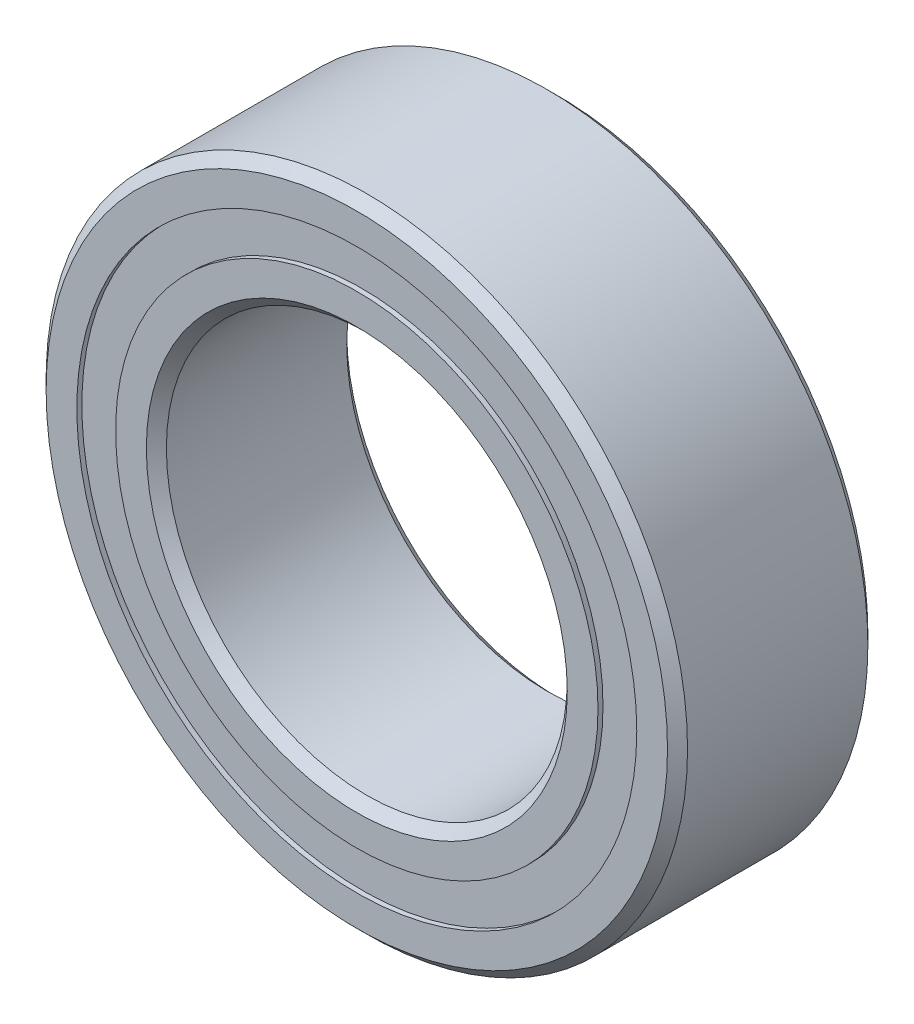
SolidWorks part; units mm, degrees
ref_plane "Front Plane" through (0, 0, 0) normal (0, 0, 1) x (1, 0, 0)
ref_plane "Top Plane" through (0, 0, 0) normal (0, 1, 0) x (1, 0, 0)
ref_plane "Right Plane" through (0, 0, 0) normal (1, 0, 0) x (0, 0, -1)
sketch "Sketch1" plane through (0, 0, 0) normal (1, 0, 0) x (0, 0, -1)
  line L0 (-1.9837, 0) -> (1.9837, 0) construction
  line L1 (0, 6.35) -> (0, -6.35) construction
  line L2 (1.7854, 6.35) -> (-1.7854, 6.35)
  line L3 (-1.7854, 6.35) -> (-1.9837, 6.1516)
  line L4 (-1.9837, 6.1516) -> (-1.9837, 5.5432)
  line L5 (-1.9837, 5.5432) -> (-0.8817, 5.5432)
  line L6 (1.9837, 5.5432) -> (0.8817, 5.5432)
  line L7 (1.9837, 6.1516) -> (1.9837, 5.5432)
  line L8 (1.7854, 6.35) -> (1.9837, 6.1516)
  line L9 (0, 6.35) -> (0, 5.1594) construction
  line L10 (0, 5.1594) -> (0, 3.9688) construction
  arc A0 (-0.8817, 5.5432) -> (0.8817, 5.5432) centre (0, 5.1594) cw
  point P14 (0, 3.9688)
  dimension "D3" = 1.7633
  dimension "D1" = 45
  dimension "Width" = 3.9675
  dimension "OD" = 12.7
  dimension "D2" = 0.1984
  dimension "Shaft Dia" = 7.9375
  dimension "D4" = 0.3838
revolve "Revolve1" add sketch "Sketch1" angle 360 about L0
sketch "Sketch3" plane through (0, 0, 0) normal (1, 0, 0) x (0, 0, -1)
  line L0 (-0.8817, 4.7755) -> (-1.9837, 4.7755)
  line L1 (-1.9837, 6.1516) -> (-1.9837, 5.5432) construction
  line L2 (-1.7854, 6.35) -> (-1.9837, 6.1516) construction
  line L3 (-1.9837, 4.7755) -> (-1.9837, 4.1671)
  line L5 (-1.9837, 4.1671) -> (-1.7854, 3.9688)
  line L6 (-1.7854, 3.9688) -> (1.7854, 3.9688)
  line L7 (1.7854, 6.35) -> (1.7854, -6.35) construction
  line L8 (1.7854, 3.9688) -> (1.9837, 4.1671)
  line L9 (1.9837, -6.1516) -> (1.9837, 6.1516) construction
  line L10 (1.9837, 4.1671) -> (1.9837, 4.7755)
  line L11 (1.9837, 4.7755) -> (0.8817, 4.7755)
  line L12 (0, 6.35) -> (0, -6.35) construction
  line L13 (1.7854, 6.35) -> (1.9837, 6.1516) construction
  arc A1 (0.8817, 4.7755) -> (-0.8817, 4.7755) centre (0, 5.1594) cw
  arc A2 (0.8817, 5.5432) -> (-0.8817, 5.5432) centre (0, 5.1594) ccw construction
revolve "Revolve3" add sketch "Sketch3" angle 360 about L0
sketch "Sketch4" plane through (0, 0, 0) normal (1, 0, 0) x (0, 0, -1)
  line L0 (-0.9616, 5.1594) -> (0.9616, 5.1594)
  arc A2 (-0.9616, 5.1594) -> (0.9616, 5.1594) centre (0, 5.1594) cw
  arc A3 (0.8817, 5.5432) -> (-0.8817, 5.5432) centre (0, 5.1594) ccw construction
revolve "Revolve4" add sketch "Sketch4" angle 360 about L0
ref_axis "Axis1" through (0, 0, -1.9837) along (0, 0, 1)
pattern_circular "CirPattern1" count 16 every 22.5 about axis through (0, 0, -1.9837) along (0, 0, 1) of bodies 104
sketch "Sketch5" plane through (0, 0, 0) normal (1, 0, 0) x (0, 0, -1)
  line L0 (-1.9837, 5.5432) -> (-0.8817, 5.5432) construction
  line L1 (-1.8846, 5.5432) -> (-0.9616, 5.5432)
  line L2 (-1.8846, 5.5432) -> (-1.8846, 4.7755)
  line L3 (-1.8846, 4.7755) -> (-0.9616, 4.7755)
  line L4 (-0.9616, 5.5432) -> (-0.9616, 4.7755)
  line L5 (-0.8817, 4.7755) -> (-1.9837, 4.7755) construction
  line L6 (1.9837, 5.5432) -> (0.8817, 5.5432) construction
  line L7 (1.8846, 5.5432) -> (0.9616, 5.5432)
  line L8 (1.8846, 5.5432) -> (1.8846, 4.7755)
  line L9 (1.8846, 4.7755) -> (0.9616, 4.7755)
  line L10 (0.9616, 5.5432) -> (0.9616, 4.7755)
  line L11 (1.9837, 4.7755) -> (0.8817, 4.7755) construction
  line L12 (-1.7854, 6.35) -> (-1.9837, 6.1516) construction
  point P18 (-1.8846, 6.2508)
revolve "Revolve5" add sketch "Sketch5" angle 360 about L0
equation "\"D2@Sketch1\" = \"Width@Sketch1\"*.05"
equation "\"D3@Sketch1\" = \"Width@Sketch1\"/2.25"
equation "\"D4@Sketch1\" = (((\"OD@Sketch1\"-\"Width@Sketch1\")/2)/3.25)/3.5"
equation "\"D2@CirPattern1\" = 360/\"Balls@CirPattern1\""
